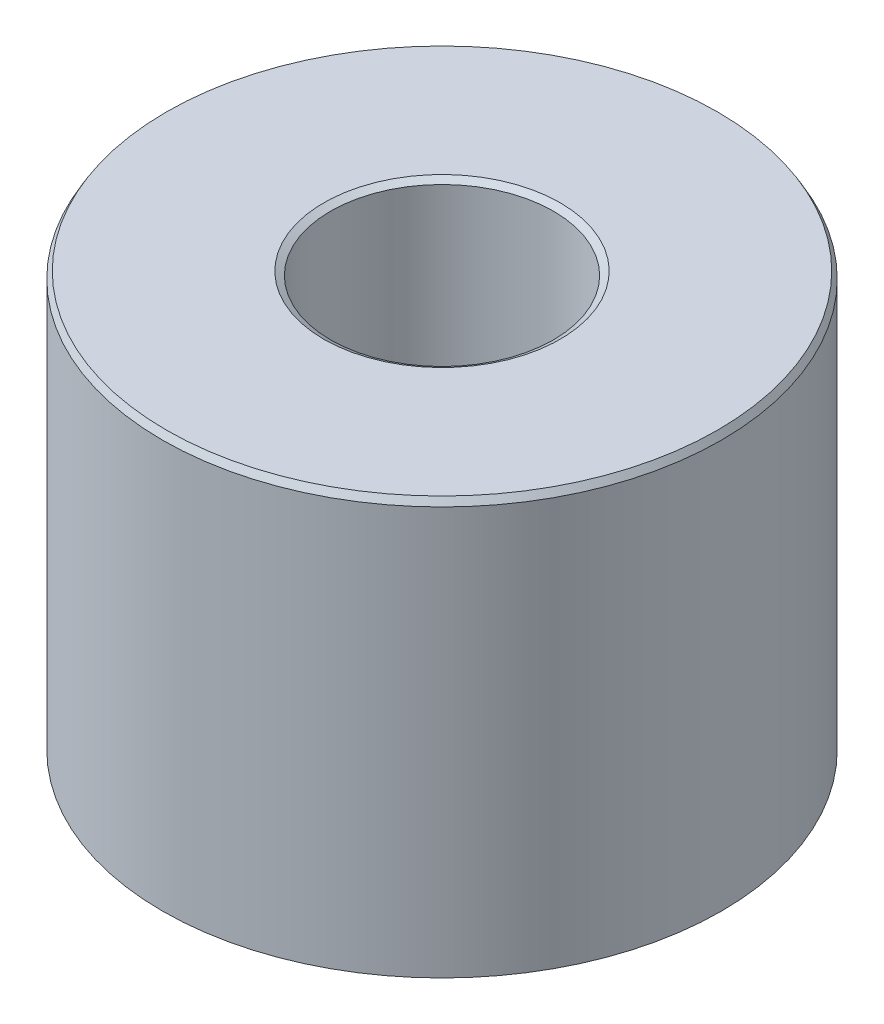
SolidWorks part; units mm, degrees
ref_plane "Front Plane" through (0, 0, 0) normal (0, 0, 1) x (1, 0, 0)
ref_plane "Top Plane" through (0, 0, 0) normal (0, 1, 0) x (1, 0, 0)
ref_plane "Right Plane" through (0, 0, 0) normal (1, 0, 0) x (0, 0, -1)
sketch "Sketch1" plane through (0, 0, 0) normal (0, 1, 0) x (1, 0, 0)
  circle A0 centre (0, 0) radius 25
  dimension "SLEEVE_OD" = 50
extrude "Boss-Extrude1" add sketch "Sketch1" along normal blind 37.4391
sketch "Sketch2" plane through (0, 0, 0) normal (0, 1, 0) x (1, 0, 0)
  circle A0 centre (0, 0) radius 9.9727
  dimension "BORE_D" = 19.9454
extrude "Cut-Extrude1" cut sketch "Sketch2" along normal through all
chamfer "Chamfer1" distance 0.6024 angle 30 4 edges at (0, 37.4391, 9.9727) (0, 0, 9.9727) (0, 0, 25) (0, 37.4391, 25) first distance on face at (0, 37.4391, 9.9727) first distance on face at (0, 0, 9.9727) first distance on face at (0, 37.4391, 25)
